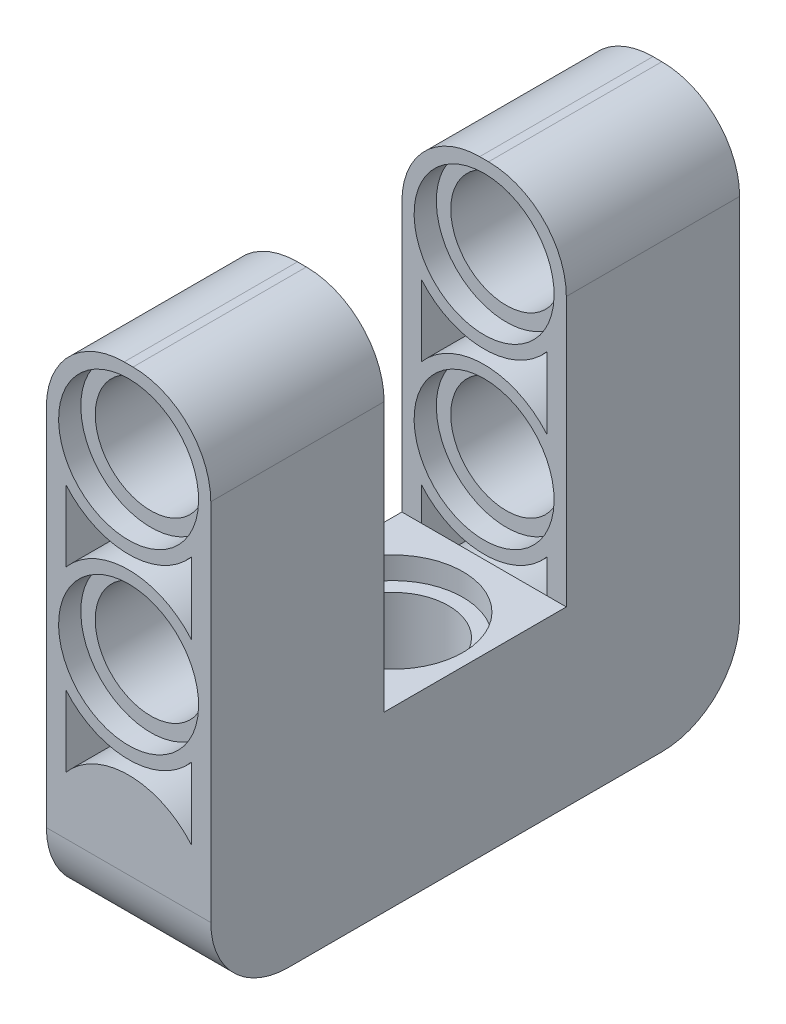
SolidWorks part; units mm, degrees
ref_plane "前视基准面" through (0, 0, 0) normal (0, 0, 1) x (1, 0, 0)
ref_plane "上视基准面" through (0, 0, 0) normal (0, 1, 0) x (1, 0, 0)
ref_plane "右视基准面" through (0, 0, 0) normal (1, 0, 0) x (0, 0, -1)
other "Configuration Table"
sketch "草图3" plane through (0, 0, 0) normal (1, 0, 0) x (0, 0, -1)
  line L0 (-4.1, 0) -> (-4, 0)
  line L5 (-4, 7.8) -> (4, 7.8)
  line L6 (-4, 7.8) -> (-4, 0)
  line L7 (-4, 0) -> (4, 0)
  line L8 (4, 7.8) -> (4, 0)
  line L13 (-11.9, 23.4) -> (-4.1, 23.4)
  line L14 (-11.9, 23.4) -> (-11.9, 0)
  line L15 (-11.9, 0) -> (-4.1, 0)
  line L16 (-4.1, 23.4) -> (-4.1, 0)
  line L17 (4.1, 23.4) -> (11.9, 23.4)
  line L18 (4.1, 23.4) -> (4.1, 0)
  line L19 (4.1, 0) -> (11.9, 0)
  line L20 (11.9, 23.4) -> (11.9, 0)
  line L21 (-4, 7.8) -> (-4.1, 7.8)
  line L22 (4, 7.8) -> (4.1, 7.8)
  line L23 (4, 0) -> (4.1, 0)
  line L24 (-8, 23.4) -> (-8, 0) construction
  line L26 (0, 7.8) -> (0, 0) construction
  dimension "D1" = 8
  dimension "D2" = 7.8
  dimension "D3" = 7.8
  dimension "D4" = 8
  dimension "D5" = 23.4
extrude "凸台-拉伸1" add sketch "草图3" along normal blind 7.4 contours L16 L13 L14 L15 | L20 L17 L18 L19 | L8 L5 L6 L7 | L6 L21 L16 L0 | L8 L23 L18 L22 region at (0, 3.9, 4.05) region at (0, 11.7, 8) region at (0, 3.9, 0) region at (0, 3.9, -4.05) region at (0, 11.7, -8)
sketch "草图4" plane through (0, 7.8, 0) normal (0, 1, 0) x (1, 0, 0)
  line L0 (3.7, 4.1) -> (3.7, -4.1) construction
  line L1 (7.4, 4.1) -> (0, 4.1) construction
  line L2 (7.4, -4.1) -> (0, -4.1) construction
  line L3 (0, 0) -> (7.4, 0) construction
  line L4 (7.4, -4.1) -> (7.4, 4.1) construction
  circle A0 centre (3.7, 0) radius 2.5
  circle A1 centre (3.7, 0) radius 3.15
  circle A2 centre (3.7, 0) radius 3.7
  dimension "D1" = 7.4
  dimension "D2" = 6.3
  dimension "D3" = 5
extrude "切除-拉伸1" cut sketch "草图4" against normal up to next contours A0 region at (3.7, 7.8, 0)
extrude "切除-拉伸2" cut sketch "草图4<3>" against normal blind 1 contours A1 A0 region at (0.6391, 7.8, 0)
sketch "草图4<3>" plane through (0, 7.8, 0) normal (0, 1, 0) x (1, 0, 0) same geometry as "草图4"
extrude "切除-拉伸3" cut sketch "草图4<4>" along normal blind 1 from surface contours A1 A0 region at (0.6391, 7.8, 0) starting at face at (3.7, 0, 2.5)
sketch "草图4<4>" plane through (0, 7.8, 0) normal (0, 1, 0) x (1, 0, 0) same geometry as "草图4"
sketch "草图5" plane through (0, 0, -11.9) normal (0, 0, -1) x (-1, 0, 0)
  line L0 (-3.7, 23.4) -> (-3.7, 0) construction
  line L1 (-7.4, 23.4) -> (0, 23.4) construction
  line L2 (-7.4, 0) -> (0, 0) construction
  line L3 (-7.4, 11.7) -> (0, 11.7) construction
  line L4 (-7.4, 23.4) -> (-7.4, 0) construction
  line L5 (0, 23.4) -> (0, 0) construction
  circle A0 centre (-3.7, 11.7) radius 2.5
  circle A1 centre (-3.7, 11.7) radius 3.15
  circle A2 centre (-3.7, 11.7) radius 3.7
  dimension "D1" = 7.4
  dimension "D2" = 6.3
  dimension "D3" = 5
extrude "切除-拉伸4" cut sketch "草图5" against normal through all contours A0 region at (3.7, 11.7, -11.9)
extrude "切除-拉伸5" cut sketch "草图5<3>" against normal blind 1 contours A1 A0 region at (6.7609, 11.7, -11.9)
sketch "草图5<3>" plane through (0, 0, -11.9) normal (0, 0, -1) x (-1, 0, 0) same geometry as "草图5"
extrude "切除-拉伸6" cut sketch "草图5<4>" along normal blind 1 from surface contours A1 A0 region at (6.7609, 11.7, -11.9) starting at face at (3.7, 14.2, -4.1)
sketch "草图5<4>" plane through (0, 0, -11.9) normal (0, 0, -1) x (-1, 0, 0) same geometry as "草图5"
extrude "切除-拉伸7" cut sketch "草图5<5>" against normal blind 1 from surface contours A1 A0 region at (6.7609, 11.7, -11.9) starting at face at (3.7, 14.2, 4.1)
sketch "草图5<5>" plane through (0, 0, -11.9) normal (0, 0, -1) x (-1, 0, 0) same geometry as "草图5"
extrude "切除-拉伸8" cut sketch "草图5<6>" along normal blind 1 from surface contours A1 A0 region at (6.7609, 11.7, -11.9) starting at face at (1.2, 11.7, 11.9)
sketch "草图5<6>" plane through (0, 0, -11.9) normal (0, 0, -1) x (-1, 0, 0) same geometry as "草图5"
pattern_linear "阵列(线性)1" count 2 spacing 8 along (0, 1, 0) of "切除-拉伸4", "切除-拉伸5", "切除-拉伸6", "切除-拉伸7", "切除-拉伸8"
sketch "草图6" plane through (0, 0, -11.9) normal (0, 0, -1) x (-1, 0, 0)
  line L0 (-3.7, 23.4) -> (-3.7, 0) construction
  line L1 (-7.4, 23.4) -> (0, 23.4) construction
  line L2 (-7.4, 0) -> (0, 0) construction
  line L3 (-7.4, 11.7) -> (0, 11.7) construction
  line L4 (-7.4, 23.4) -> (-7.4, 0) construction
  line L5 (0, 23.4) -> (0, 0) construction
  line L6 (-1.2, 11.7) -> (-0.55, 11.7)
  line L7 (-6.85, 11.7) -> (-6.2, 11.7)
  line L8 (-6.525, 11.7) -> (-6.525, 17.3106)
  line L9 (-0.875, 11.7) -> (-0.875, 17.3106)
  circle A0 centre (-3.7, 11.7) radius 2.5
  circle A1 centre (-3.7, 11.7) radius 3.15
  circle A2 centre (-3.7, 11.7) radius 3.7
  circle A3 centre (-3.7, 19.7) radius 3.7
  dimension "D1" = 7.4
  dimension "D2" = 6.3
  dimension "D3" = 5
  dimension "D4" = 7.4
  dimension "D5" = 8
extrude "切除-拉伸9" cut sketch "草图6" against normal blind 2 contours A3 L8 A2 L9 region at (3.7, 15.7, -11.9)
extrude "切除-拉伸10" cut sketch "草图6<3>" along normal blind 2 from surface contours A3 L8 A2 L9 region at (3.7, 15.7, -11.9) starting at face at (3.7, 14.85, -4.1)
sketch "草图6<3>" plane through (0, 0, -11.9) normal (0, 0, -1) x (-1, 0, 0) same geometry as "草图6"
extrude "切除-拉伸11" cut sketch "草图6<4>" against normal blind 2 from surface contours A3 L8 A2 L9 region at (3.7, 15.7, -11.9) starting at face at (3.7, 22.85, 4.1)
sketch "草图6<4>" plane through (0, 0, -11.9) normal (0, 0, -1) x (-1, 0, 0) same geometry as "草图6"
extrude "切除-拉伸12" cut sketch "草图6<5>" along normal blind 2 from surface contours A3 L8 A2 L9 region at (3.7, 15.7, -11.9) starting at face at (3.7, 14.85, 11.9)
sketch "草图6<5>" plane through (0, 0, -11.9) normal (0, 0, -1) x (-1, 0, 0) same geometry as "草图6"
pattern_linear "阵列(线性)2" count 2 spacing 8 along (0, -1, 0) of "切除-拉伸9", "切除-拉伸10", "切除-拉伸11", "切除-拉伸12"
fillet "圆角1" radius 3.5 6 edges at (0, 23.4, 8) (7.4, 23.4, 8) (0, 23.4, -8) (7.4, 23.4, -8) (3.7, 0, -11.9) (3.7, 0, 11.9)
